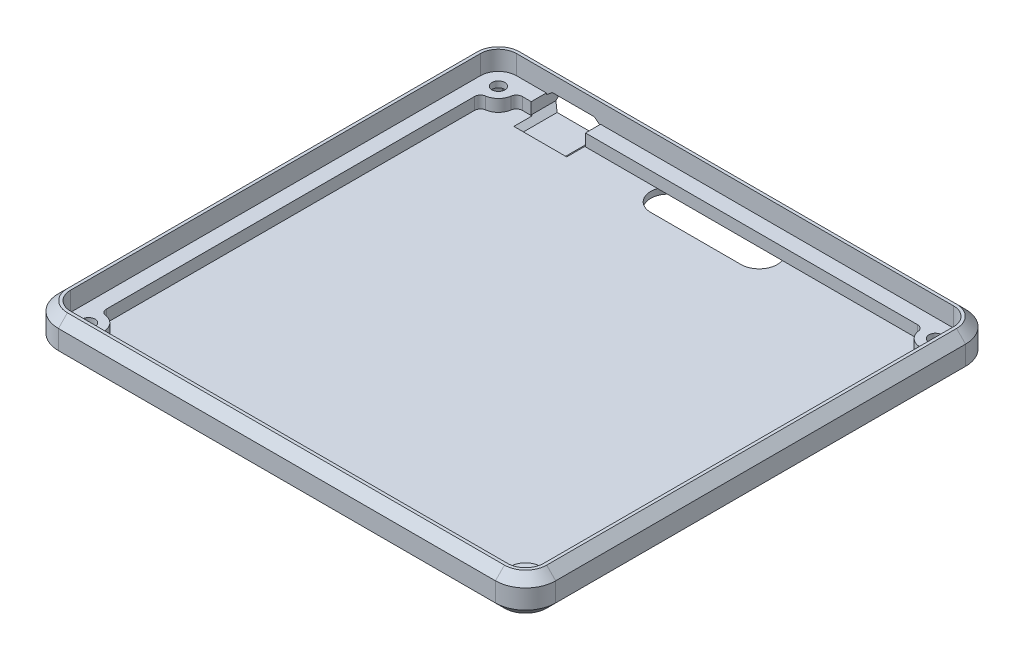
SolidWorks part; units mm, degrees
material "ABS"
ref_plane "Front Plane" through (0, 0, 0) normal (0, 0, 1) x (1, 0, 0)
ref_plane "Top Plane" through (0, 0, 0) normal (0, 1, 0) x (1, 0, 0)
ref_plane "Right Plane" through (0, 0, 0) normal (1, 0, 0) x (0, 0, -1)
sketch "Sketch2" plane through (0, 0, 0) normal (0, 1, 0) x (1, 0, 0)
  line L1 (-72.5, 74) -> (72.5, 74)
  line L2 (-78.5, 68) -> (-78.5, -68)
  line L3 (-72.5, -74) -> (72.5, -74)
  line L4 (78.5, 68) -> (78.5, -68)
  line L5 (-78.5, 74) -> (78.5, -74) construction
  line L6 (-78.5, -74) -> (78.5, 74) construction
  arc A0 (-78.5, -68) -> (-72.5, -74) centre (-72.5, -68) ccw
  arc A1 (-72.5, 74) -> (-78.5, 68) centre (-72.5, 68) ccw
  arc A2 (72.5, 74) -> (78.5, 68) centre (72.5, 68) cw
  arc A3 (72.5, -74) -> (78.5, -68) centre (72.5, -68) ccw
  point P0 (0, 0)
  dimension "D3" = 6
  dimension "D1" = 157
  dimension "D2" = 148
extrude "Boss-Extrude2" add sketch "Sketch2" along normal blind 2
sketch "Sketch3" plane through (0, 2, 0) normal (0, 1, 0) x (1, 0, 0)
  line L0 (-72.5, -74) -> (72.5, -74) construction
  line L1 (78.5, -68) -> (78.5, 68) construction
  line L2 (72.5, 74) -> (-72.5, 74) construction
  line L3 (-78.5, 68) -> (-78.5, -68) construction
  line L4 (-72.5, -74) -> (72.5, -74)
  line L5 (78.5, -68) -> (78.5, 68)
  line L6 (72.5, 74) -> (-72.5, 74)
  line L7 (-78.5, 68) -> (-78.5, -68)
  line L8 (0, -80.5945) -> (0, 82.9206) construction
  line L9 (9.041, 0) -> (-113.0904, 0) construction
  line L10 (-82.5, 68) -> (-82.5, -68)
  line L11 (-72.5, -78) -> (72.5, -78)
  line L12 (82.5, -68) -> (82.5, 68)
  line L13 (72.5, 78) -> (-72.5, 78)
  line L14 (-73.5, 63) -> (-73.5, -63)
  line L15 (-67.5, -69) -> (67.5, -69)
  line L16 (73.5, -63) -> (73.5, 63)
  line L17 (67.5, 69) -> (-67.5, 69)
  line L18 (-73.5, 63) -> (-72.5, 63)
  line L19 (-67.5, 69) -> (-67.5, 68)
  line L20 (-73.5, 68) -> (-73.5, -68) construction
  line L21 (72.5, 69) -> (-72.5, 69) construction
  line L22 (67.5, 69) -> (67.5, 68)
  line L23 (73.5, 63) -> (72.5, 63)
  line L24 (67.5, -69) -> (67.5, -68)
  line L25 (73.5, -63) -> (72.5, -63)
  line L26 (-67.5, -69) -> (-67.5, -68)
  line L27 (-73.5, -63) -> (-72.5, -63)
  line L28 (-72.5, -69) -> (72.5, -69) construction
  line L29 (73.5, -68) -> (73.5, 68) construction
  arc A0 (-78.5, -68) -> (-72.5, -74) centre (-72.5, -68) ccw construction
  arc A1 (72.5, -74) -> (78.5, -68) centre (72.5, -68) ccw construction
  arc A2 (78.5, 68) -> (72.5, 74) centre (72.5, 68) ccw construction
  arc A3 (-72.5, 74) -> (-78.5, 68) centre (-72.5, 68) ccw construction
  arc A4 (-78.5, -68) -> (-72.5, -74) centre (-72.5, -68) ccw
  arc A5 (72.5, -74) -> (78.5, -68) centre (72.5, -68) ccw
  arc A6 (78.5, 68) -> (72.5, 74) centre (72.5, 68) ccw
  arc A7 (-72.5, 74) -> (-78.5, 68) centre (-72.5, 68) ccw
  circle A9 centre (-72.5, -68) radius 2.15
  circle A10 centre (72.5, -68) radius 2.15
  circle A11 centre (72.5, 68) radius 2.15
  circle A12 centre (-72.5, 68) radius 2.15
  arc A13 (-82.5, -68) -> (-72.5, -78) centre (-72.5, -68) ccw
  arc A14 (72.5, -78) -> (82.5, -68) centre (72.5, -68) ccw
  arc A15 (82.5, 68) -> (72.5, 78) centre (72.5, 68) ccw
  arc A16 (-72.5, 78) -> (-82.5, 68) centre (-72.5, 68) ccw
  arc A21 (-72.5, 63) -> (-67.5, 68) centre (-72.5, 68) ccw
  arc A22 (72.5, 63) -> (67.5, 68) centre (72.5, 68) cw
  arc A23 (-72.5, 69) -> (-73.5, 68) centre (-72.5, 68) ccw construction
  arc A24 (72.5, -63) -> (67.5, -68) centre (72.5, -68) ccw
  arc A25 (-72.5, -63) -> (-67.5, -68) centre (-72.5, -68) cw
  arc A26 (-73.5, -68) -> (-72.5, -69) centre (-72.5, -68) ccw construction
  arc A27 (72.5, -69) -> (73.5, -68) centre (72.5, -68) ccw construction
  arc A28 (73.5, 68) -> (72.5, 69) centre (72.5, 68) ccw construction
  arc M10 (-78.5, -68) -> (-72.5, -74) centre (-72.5, -68) ccw
  line M11 (-72.5, -74) -> (72.5, -74)
  arc M12 (72.5, -74) -> (78.5, -68) centre (72.5, -68) ccw
  line M13 (78.5, -68) -> (78.5, 68)
  arc M14 (78.5, 68) -> (72.5, 74) centre (72.5, 68) ccw
  line M15 (72.5, 74) -> (-72.5, 74)
  arc M16 (-72.5, 74) -> (-78.5, 68) centre (-72.5, 68) ccw
  line M17 (-78.5, 68) -> (-78.5, -68)
  dimension "D1" = 68
  dimension "D2" = 4.3
  dimension "D3" = 72.5
  dimension "D4" = 4
  dimension "D6" = 1
  dimension "D7" = 5
  dimension "D8" = 1
  dimension "D9" = 5
  dimension "D5" = 5
extrude "Boss-Extrude3" add sketch "Sketch3" along normal blind 4 and the other way blind 2 contours L13 A16 L10 A13 L11 A14 L12 A15 M10 M17 M16 M15 M14 M13 M12 M11 | L17 L16 L15 L14 M17 M10 M11 M12 M13 M14 M15 M16 region at (-75.217, 2, 70.717) region at (-77.9654, 2, -73.4654)
sketch "Sketch8" plane through (0, 6, 0) normal (0, 1, 0) x (1, 0, 0)
  line L0 (-72.5, -78) -> (72.5, -78) construction
  line L1 (82.5, -68) -> (82.5, 68) construction
  line L2 (72.5, 78) -> (-72.5, 78) construction
  line L3 (-82.5, 68) -> (-82.5, -68) construction
  line L4 (78.5, -68) -> (78.5, 68)
  line L5 (72.5, 74) -> (-72.5, 74)
  line L6 (-78.5, 68) -> (-78.5, -68)
  line L7 (-72.5, -74) -> (72.5, -74)
  line L8 (78.5, -68) -> (78.5, 68)
  line L9 (72.5, 74) -> (-72.5, 74)
  line L10 (-78.5, 68) -> (-78.5, -68)
  line L11 (-72.5, -74) -> (72.5, -74)
  line L12 (-72.5, -78) -> (72.5, -78)
  line L13 (82.5, -68) -> (82.5, 68)
  line L14 (72.5, 78) -> (-72.5, 78)
  line L15 (-82.5, 68) -> (-82.5, -68)
  line L16 (-77.5, 68) -> (-77.5, -68)
  line L17 (-72.5, -73) -> (72.5, -73)
  line L18 (77.5, -68) -> (77.5, 68)
  line L19 (72.5, 73) -> (-72.5, 73)
  arc A0 (-82.5, -68) -> (-72.5, -78) centre (-72.5, -68) ccw construction
  arc A1 (72.5, -78) -> (82.5, -68) centre (72.5, -68) ccw construction
  arc A2 (82.5, 68) -> (72.5, 78) centre (72.5, 68) ccw construction
  arc A3 (-72.5, 78) -> (-82.5, 68) centre (-72.5, 68) ccw construction
  arc A4 (78.5, 68) -> (72.5, 74) centre (72.5, 68) ccw
  arc A5 (-72.5, 74) -> (-78.5, 68) centre (-72.5, 68) ccw
  arc A6 (-78.5, -68) -> (-72.5, -74) centre (-72.5, -68) ccw
  arc A7 (72.5, -74) -> (78.5, -68) centre (72.5, -68) ccw
  arc A8 (78.5, 68) -> (72.5, 74) centre (72.5, 68) ccw
  arc A9 (-72.5, 74) -> (-78.5, 68) centre (-72.5, 68) ccw
  arc A10 (-78.5, -68) -> (-72.5, -74) centre (-72.5, -68) ccw
  arc A11 (72.5, -74) -> (78.5, -68) centre (72.5, -68) ccw
  arc A12 (-82.5, -68) -> (-72.5, -78) centre (-72.5, -68) ccw
  arc A13 (72.5, -78) -> (82.5, -68) centre (72.5, -68) ccw
  arc A14 (82.5, 68) -> (72.5, 78) centre (72.5, 68) ccw
  arc A15 (-72.5, 78) -> (-82.5, 68) centre (-72.5, 68) ccw
  arc A16 (-77.5, -68) -> (-72.5, -73) centre (-72.5, -68) ccw
  arc A17 (72.5, -73) -> (77.5, -68) centre (72.5, -68) ccw
  arc A18 (77.5, 68) -> (72.5, 73) centre (72.5, 68) ccw
  arc A19 (-72.5, 73) -> (-77.5, 68) centre (-72.5, 68) ccw
  line M17 (72.5, 78) -> (-72.5, 78)
  arc M18 (-72.5, 78) -> (-82.5, 68) centre (-72.5, 68) ccw
  line M19 (-82.5, 68) -> (-82.5, -68)
  arc M20 (-82.5, -68) -> (-72.5, -78) centre (-72.5, -68) ccw
  line M21 (-72.5, -78) -> (72.5, -78)
  arc M22 (72.5, -78) -> (82.5, -68) centre (72.5, -68) ccw
  line M23 (82.5, -68) -> (82.5, 68)
  arc M24 (82.5, 68) -> (72.5, 78) centre (72.5, 68) ccw
  dimension "D1" = 0
  dimension "D2" = 5
extrude "Boss-Extrude4" add sketch "Sketch8" along normal blind 6.38 contours A11 L11 A10 L10 A9 L9 A8 L8 M24 M17 M18 M19 M20 M21 M22 M23 region at (-77.9654, 6, 73.4654)
sketch "Sketch9" plane through (0, 0, -78) normal (0, 0, -1) x (-1, 0, 0)
  line L0 (82.5, 0) -> (82.5, 12.38) construction
  line L7 (60.62, 7.11) -> (46.62, 7.11)
  line L8 (46.62, 7.11) -> (44.62, 5.51)
  line L14 (62.62, 5.51) -> (60.62, 7.11)
  line L15 (54.9775, 3.85) -> (29.0731, 3.85) construction
  line L16 (44.62, 5.51) -> (44.62, 2.19)
  line L17 (62.62, 5.51) -> (62.62, 2.19)
  line L18 (53.62, 7.11) -> (53.62, 5.8424) construction
  line L19 (-72.5, 0) -> (72.5, 0) construction
  line L20 (62.62, 2.19) -> (60.62, 0.59)
  line L21 (60.62, 0.59) -> (46.62, 0.59)
  line L22 (46.62, 0.59) -> (44.62, 2.19)
  point P7 (62.62, 3.85)
  point P20 (44.62, 3.85)
  dimension "D2" = 3.85
  dimension "D1" = 28.88
  dimension "D5" = 3.26
  dimension "D6" = 1.66
  dimension "D7" = 18
  dimension "D8" = 14
extrude "Cut-Extrude1" cut sketch "Sketch9" against normal blind 15
fillet "Fillet1" radius 2 8 edges at (-67.5, 4, -69) (-73.5, 4, -63) (-73.5, 4, 63) (-67.5, 4, 69) (73.5, 4, 63) (67.5, 4, 69) (67.5, 4, -69) (73.5, 4, -63)
sketch "Sketch11" plane through (0, 2, 0) normal (0, 1, 0) x (1, 0, 0)
  circle A0 centre (-72.5, 68) radius 2.15
  circle A1 centre (72.5, 68) radius 2.15
  circle A2 centre (72.5, -68) radius 2.15
  circle A3 centre (-72.5, -68) radius 2.15
  dimension "D1" = 4.3
  dimension "D2" = 4.3
  dimension "D3" = 4.3
  dimension "D4" = 4.3
extrude "Cut-Extrude3" cut sketch "Sketch11" against normal through all both and the other way through all contours A3 | A2 | A1 | A0 region at (-72.5, 2, -68) region at (72.5, 2, -68) region at (72.5, 2, 68) region at (-72.5, 2, 68)
sketch "Sketch10" plane through (0, 0, 0) normal (0, -1, 0) x (1, 0, 0)
  line L0 (0, -78) -> (0, 105.632) construction
  line L1 (72.5, -78) -> (-72.5, -78) construction
  line L2 (-82.5, 0) -> (91.4068, 0) construction
  line L3 (-82.5, -68) -> (-82.5, 68) construction
  line L4 (70.4793, 64.5) -> (68.4585, 68)
  line L5 (-68.4585, 68) -> (-70.4793, 71.5)
  line L6 (-70.4793, 71.5) -> (-74.5207, 71.5)
  line L7 (-74.5207, 71.5) -> (-76.5415, 68)
  line L8 (-76.5415, 68) -> (-74.5207, 64.5)
  line L9 (-74.5207, 64.5) -> (-70.4793, 64.5)
  line L10 (-70.4793, 64.5) -> (-68.4585, 68)
  line L11 (74.5207, 64.5) -> (70.4793, 64.5)
  line L12 (76.5415, 68) -> (74.5207, 64.5)
  line L13 (74.5207, 71.5) -> (76.5415, 68)
  line L14 (70.4793, 71.5) -> (74.5207, 71.5)
  line L15 (68.4585, 68) -> (70.4793, 71.5)
  line L16 (74.5207, -64.5) -> (70.4793, -64.5)
  line L17 (76.5415, -68) -> (74.5207, -64.5)
  line L18 (74.5207, -71.5) -> (76.5415, -68)
  line L19 (70.4793, -71.5) -> (74.5207, -71.5)
  line L20 (68.4585, -68) -> (70.4793, -71.5)
  line L21 (70.4793, -64.5) -> (68.4585, -68)
  line L22 (-70.4793, -64.5) -> (-68.4585, -68)
  line L23 (-74.5207, -64.5) -> (-70.4793, -64.5)
  line L24 (-76.5415, -68) -> (-74.5207, -64.5)
  line L25 (-74.5207, -71.5) -> (-76.5415, -68)
  line L26 (-70.4793, -71.5) -> (-74.5207, -71.5)
  line L27 (-68.4585, -68) -> (-70.4793, -71.5)
  line L28 (-72.5, 68) -> (-62.8389, 68)
  circle A0 centre (-72.5, 68) radius 3.5 construction
  circle A1 centre (-72.5, 68) radius 2.15 construction
  dimension "D3" = 7
extrude "Cut-Extrude2" cut sketch "Sketch10" against normal blind 4 contours L9 L10 L5 L6 L7 L8 | L12 L11 L4 L15 L14 L13 | L22 L27 L26 L25 L24 L23 | L17 L16 L21 L20 L19 L18 region at (-69.5615, 0, 66.3035)
chamfer "Chamfer1" distance 3 angle 45 16 edges at (-79.5711, 12.38, 75.0711) (0, 12.38, 78) (79.5711, 12.38, 75.0711) (82.5, 12.38, 0) (79.5711, 12.38, -75.0711) (0, 12.38, -78) (-82.5, 12.38, 0) (-79.5711, 12.38, -75.0711) (-79.5711, 0, -75.0711) (-82.5, 0, 0) (-79.5711, 0, 75.0711) (0, 0, 78) (79.5711, 0, 75.0711) (82.5, 0, 0) (79.5711, 0, -75.0711) (0, 0, -78)
sketch "Sketch13" plane through (0, 6, 0) normal (0, 1, 0) x (1, 0, 0)
  line L0 (-53.62, 63) -> (-53.62, 80.4308) construction
  line L1 (-46.62, 63) -> (-60.62, 63) construction
  line L2 (-44.62, 69) -> (-62.62, 69)
  line L3 (65.5718, 69) -> (-45.2325, 69) construction
  line L4 (-62.0075, 69) -> (-65.5718, 69) construction
  line L5 (-62.62, 69) -> (-62.62, 74)
  line L6 (-62.0075, 74) -> (-72.5, 74) construction
  line L7 (-62.62, 74) -> (-44.62, 74)
  line L8 (72.5, 74) -> (-72.5, 74) construction
  line L9 (-44.62, 74) -> (-44.62, 69)
  dimension "D1" = 9
  dimension "D2" = 9
extrude "Cut-Extrude5" cut sketch "Sketch13" against normal blind 1
sketch "Sketch14" plane through (0, 0, 0) normal (0, -1, 0) x (1, 0, 0)
  line L0 (0, 15.7154) -> (0, -85.3561) construction
  line L1 (-72.5, -75) -> (72.5, -75) construction
  circle A0 centre (-60, -50) radius 10
  circle A1 centre (60, -50) radius 10
  dimension "D1" = 20
  dimension "D2" = 60
  dimension "D3" = 25
extrude "Cut-Extrude6" cut sketch "Sketch14" against normal blind 1
sketch "Sketch15" plane through (0, 0, 0) normal (0, -1, 0) x (1, 0, 0)
  line L0 (0, 10.9905) -> (0, -88.4375) construction
  line L1 (-15, -67) -> (15, -67) construction
  line L2 (-15, -61) -> (15, -61)
  line L3 (-15, -73) -> (15, -73)
  line L4 (-72.5, -75) -> (72.5, -75) construction
  arc A0 (-15, -61) -> (-15, -73) centre (-15, -67) ccw
  arc A1 (15, -73) -> (15, -61) centre (15, -67) ccw
  point P5 (0, -67)
  dimension "D1" = 8
  dimension "D2" = 12
  dimension "D3" = 30
extrude "Cut-Extrude7" cut sketch "Sketch15" against normal blind 2
